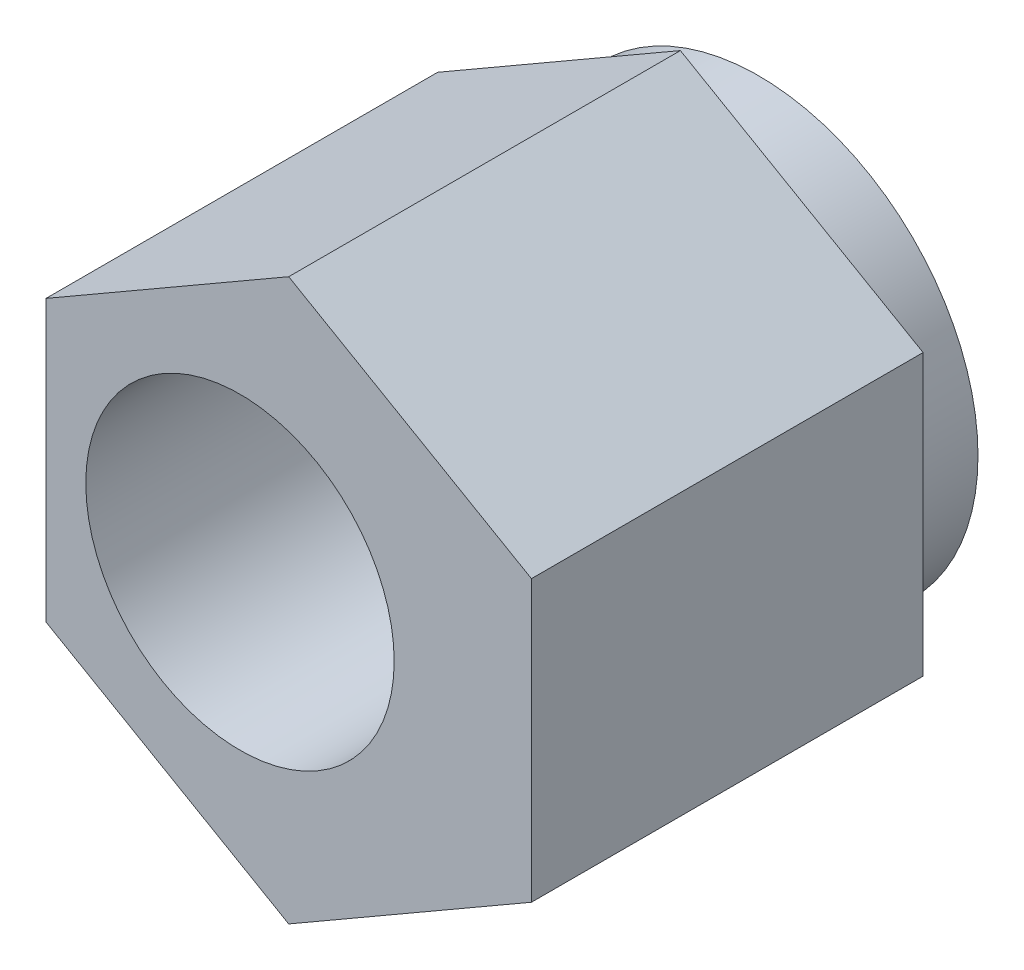
SolidWorks part; units mm, degrees
material "Chrome Stainless Steel"
ref_plane "Front Plane" through (0, 0, 0) normal (0, 0, 1) x (1, 0, 0)
ref_plane "Top Plane" through (0, 0, 0) normal (0, 1, 0) x (1, 0, 0)
ref_plane "Right Plane" through (0, 0, 0) normal (1, 0, 0) x (0, 0, -1)
sketch "Sketch1" plane through (0, 0, 0) normal (0, 0, 1) x (1, 0, 0)
  line L0 (0.79, 0) -> (0, 0) construction
  line L2 (0.79, 4.5437) -> (-3.145, 2.2719)
  line L3 (-3.145, 2.2719) -> (-3.145, -2.2719)
  line L4 (-3.145, -2.2719) -> (0.79, -4.5437)
  line L5 (0.79, -4.5437) -> (4.725, -2.2719)
  line L6 (4.725, -2.2719) -> (4.725, 2.2719)
  line L7 (4.725, 2.2719) -> (0.79, 4.5437)
  circle A0 centre (0, 0) radius 2.5
  circle A1 centre (0.79, 0) radius 3.555
  circle A2 centre (0.79, 0) radius 3.935 construction
  dimension "D1" = 5
  dimension "D2" = 0.79
  dimension "D3" = 7.87
  dimension "D4" = 7.11
extrude "Boss-Extrude3" add sketch "Sketch1" along normal blind 6.35 contours L6 L7 L2 L3 L4 L5 A1 | A1 A0 region at (2.6974, 3.3037, 0) region at (-2.6644, 0, 0)
extrude "Boss-Extrude4" add sketch "Sketch1<5>" against normal blind 1.27 contours A1 A0 region at (-2.6644, 0, 0)
sketch "Sketch1<5>" plane through (0, 0, 0) normal (0, 0, 1) x (1, 0, 0) same geometry as "Sketch1"
